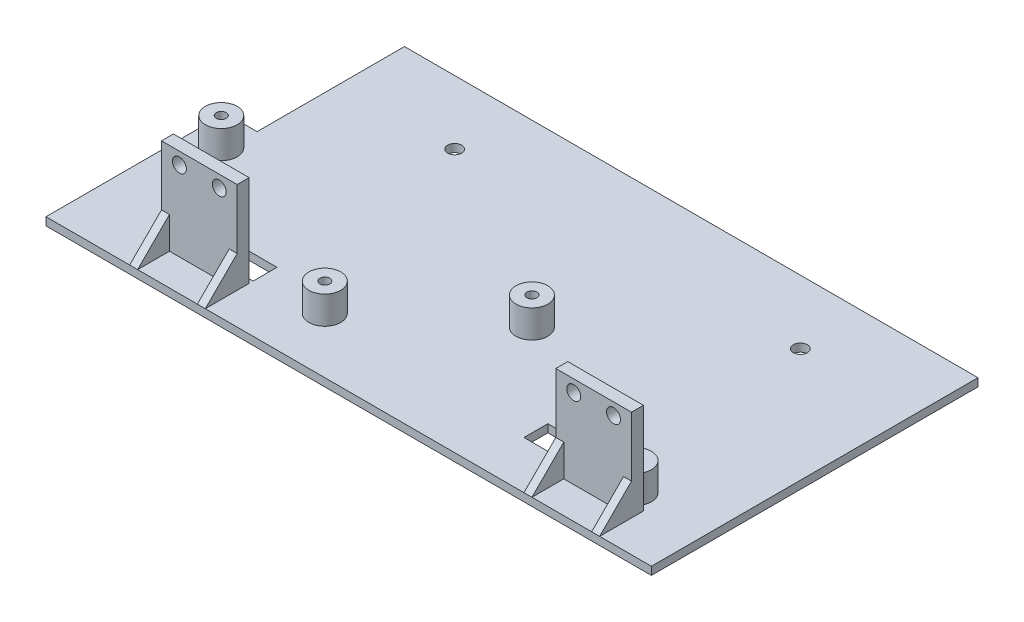
SolidWorks part; units mm, degrees
ref_plane "Alzado" through (0, 0, 0) normal (0, 0, 1) x (1, 0, 0)
ref_plane "Planta" through (0, 0, 0) normal (0, 1, 0) x (1, 0, 0)
ref_plane "Vista lateral" through (0, 0, 0) normal (1, 0, 0) x (0, 0, -1)
sketch "Croquis1" plane through (0, 0, 0) normal (0, 1, 0) x (1, 0, 0)
  line L1 (-72, 41) -> (72, 41)
  line L2 (-72, 41) -> (-72, -41)
  line L3 (-72, -41) -> (72, -41)
  line L4 (72, 41) -> (72, -41)
  line L5 (-72, 41) -> (72, -41) construction
  line L6 (-72, -41) -> (72, 41) construction
  point P0 (0, 0)
  dimension "D1" = 144
  dimension "D2" = 82
extrude "Saliente-Extruir1" add sketch "Croquis1" along normal blind 2
sketch "Croquis3" plane through (0, 2, 0) normal (0, 1, 0) x (1, 0, 0)
  line L1 (-72, -41) -> (-80, -41)
  line L2 (-72, -41) -> (-72, 4)
  line L3 (-72, 4) -> (-80, 4)
  line L4 (-80, -41) -> (-80, 4)
  dimension "D1" = 8
  dimension "D2" = 45
extrude "Saliente-Extruir2" add sketch "Croquis3" against normal blind 2
sketch "Croquis2" plane through (0, 2, 0) normal (0, 1, 0) x (1, 0, 0)
  line L0 (-80, -41) -> (72, -41) construction
  line L5 (72, -41) -> (72, 41) construction
  line L6 (-72, 41) -> (-72, 4) construction
  line L9 (-77.4631, -27) -> (87.9636, -27) construction
  line L10 (-97.4179, -4) -> (94.5346, -4) construction
  circle A0 centre (54, -27) radius 1.25
  circle A1 centre (-24, -27) radius 1.25
  circle A2 centre (-73, -4) radius 1.25
  circle A3 centre (5, -4) radius 1.25
  circle A4 centre (54, -27) radius 4
  circle A5 centre (5, -4) radius 4
  circle A6 centre (-24, -27) radius 4
  circle A7 centre (-73, -4) radius 4
  dimension "D9" = 2.5
  dimension "D2" = 8
  dimension "D6" = 14
  dimension "D7" = 48
  dimension "D8" = 18
  dimension "D10" = 23
  dimension "D11" = 49
  dimension "D12" = 49
extrude "Saliente-Extruir3" add sketch "Croquis2" along normal blind 7
sketch "Croquis4" plane through (0, 2, 0) normal (0, 1, 0) x (1, 0, 0)
  line L0 (-59, -23) -> (47, -23) construction
  line L5 (-80, -41) -> (72, -41) construction
  line L10 (72, -41) -> (72, 41) construction
  line L20 (-59, -23) -> (-40, -23)
  line L21 (-59, -23) -> (-59, -29)
  line L22 (-59, -29) -> (-40, -29)
  line L23 (-40, -23) -> (-40, -29)
  line L24 (28, -23) -> (47, -23)
  line L25 (28, -23) -> (28, -29)
  line L26 (28, -29) -> (47, -29)
  line L27 (47, -23) -> (47, -29)
  line L28 (-80, 4) -> (-80, -41) construction
  dimension "D1" = 18
  dimension "D2" = 6
  dimension "D3" = 6
  dimension "D4" = 25
  dimension "D5" = 19
  dimension "D6" = 21
  dimension "D7" = 19
extrude "Cortar-Extruir1" cut sketch "Croquis4" against normal up to next
sketch "Croquis5" plane through (0, 2, 0) normal (0, 1, 0) x (1, 0, 0)
  line L0 (-111.0382, 25) -> (96.9105, 25) construction
  line L1 (72, 41) -> (-72, 41) construction
  line L2 (0, 0) -> (0, 50.881) construction
  circle A0 centre (-43.4, 25) radius 1.75
  circle A1 centre (43.4, 25) radius 1.75
  point P9 (0, 0)
  point P10 (0, 0)
  dimension "D2" = 3.5
  dimension "D1" = 16
  dimension "D3" = 43.4
extrude "Cortar-Extruir2" cut sketch "Croquis5" against normal up to next
sketch "Croquis7" plane through (0, 2, 0) normal (0, 1, 0) x (1, 0, 0)
  line L0 (-59, -29) -> (-59, -41) construction
  line L5 (0, 0) -> (0, -59.7573) construction
  line L6 (-40, -29) -> (-40, -41) construction
  line L11 (-80, -41) -> (72, -41) construction
  line L12 (40, -29) -> (40, -41) construction
  line L13 (-59, -30) -> (-40, -30)
  line L14 (-59, -30) -> (-59, -33)
  line L15 (-59, -33) -> (-40, -33)
  line L16 (-40, -30) -> (-40, -33)
  line L17 (59, -29) -> (59, -41) construction
  line L18 (40, -30) -> (40, -33)
  line L19 (59, -33) -> (40, -33)
  line L20 (59, -30) -> (59, -33)
  line L21 (59, -30) -> (40, -30)
  dimension "D1" = 3
  dimension "D2" = 11
extrude "Saliente-Extruir4" add sketch "Croquis7" along normal blind 23
sketch "Croquis9" plane through (0, 0, 33) normal (0, 0, 1) x (1, 0, 0)
  line L0 (-49.5, 25) -> (-49.5, 2) construction
  line L1 (-59, 25) -> (-40, 25) construction
  line L2 (-59, 2) -> (-40, 2) construction
  line L3 (-59, 22) -> (-40, 22) construction
  line L4 (-59, 25) -> (-59, 2) construction
  line L5 (-40, 25) -> (-40, 2) construction
  line L6 (0, 0) -> (0, 40.7634) construction
  circle A0 centre (-54.5, 22) radius 1.75
  circle A1 centre (-44.5, 22) radius 1.75
  circle A2 centre (44.5, 22) radius 1.75
  circle A3 centre (54.5, 22) radius 1.75
  dimension "D2" = 3.5
  dimension "D1" = 3
  dimension "D3" = 5
extrude "Cortar-Extruir3" cut sketch "Croquis9" against normal up to next
sketch "Croquis10" plane through (-59, 0, 0) normal (-1, 0, 0) x (0, 0, 1)
  line L0 (41, 2) -> (33, 10)
  line L1 (33, 25) -> (33, 2) construction
  line L2 (-4, 2) -> (41, 2) construction
  dimension "D1" = 45
rib "Nervio1" sketch "Croquis10" sketch "Croquis10" thickness 2 extrusion direction parallel to sketch draft on no parameters "D1"=2
sketch "Croquis11" plane through (-40, 0, 0) normal (1, 0, 0) x (0, 0, -1)
  line L0 (-41, 2) -> (-33, 10)
rib "Nervio2" sketch "Croquis11" sketch "Croquis11" thickness 2 extrusion direction parallel to sketch draft on no parameters "D1"=2
sketch "Croquis12" plane through (59, 0, 0) normal (1, 0, 0) x (0, 0, -1)
  line L0 (-33, 10) -> (-41, 2)
rib "Nervio3" sketch "Croquis12" sketch "Croquis12" thickness 2 extrusion direction parallel to sketch draft on no parameters "D1"=2
sketch "Croquis13" plane through (40, 0, 0) normal (-1, 0, 0) x (0, 0, 1)
  line L0 (33, 10) -> (41, 2)
rib "Nervio4" sketch "Croquis13" sketch "Croquis13" thickness 2 extrusion direction parallel to sketch draft on no parameters "D1"=2
